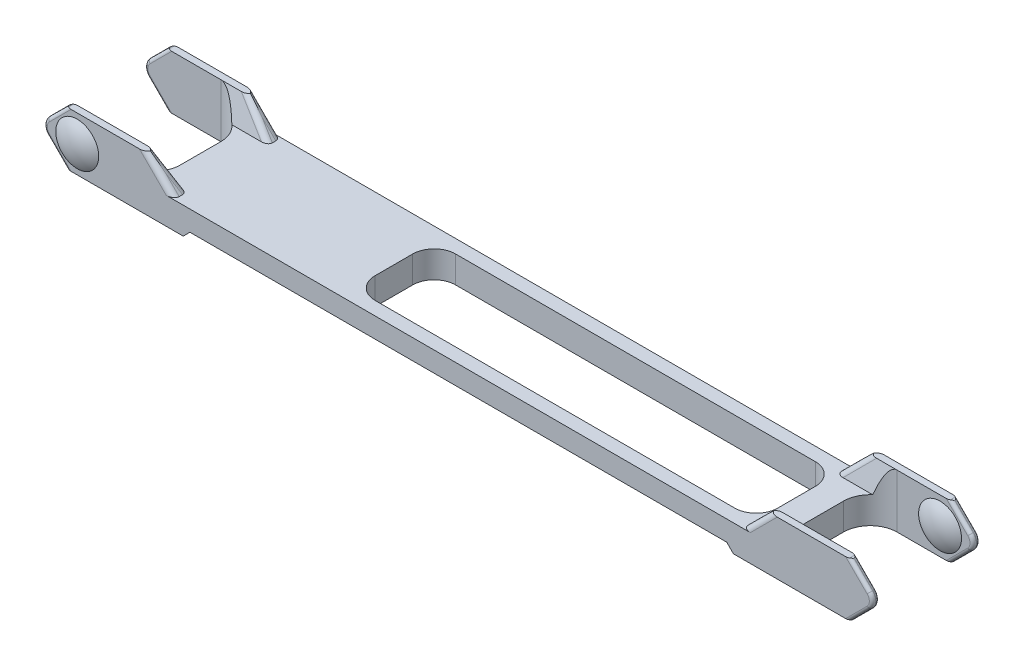
SolidWorks part; units mm, degrees
ref_plane "Front Plane" through (0, 0, 0) normal (0, 0, 1) x (1, 0, 0)
ref_plane "Top Plane" through (0, 0, 0) normal (0, 1, 0) x (1, 0, 0)
ref_plane "Right Plane" through (0, 0, 0) normal (1, 0, 0) x (0, 0, -1)
sketch "Sketch1" plane through (0, 0, 0) normal (0, 1, 0) x (1, 0, 0)
  line L0 (-73.66, 12.7) -> (-73.66, -12.7) construction
  line L1 (-99.06, -12.7) -> (99.06, -12.7)
  line L2 (-99.06, -12.7) -> (-99.06, -11.1125)
  line L3 (-99.06, 12.7) -> (99.06, 12.7)
  line L5 (-99.06, -12.7) -> (99.06, 12.7) construction
  line L6 (-99.06, 12.7) -> (99.06, -12.7) construction
  line L7 (-99.06, 11.1125) -> (-80.01, 11.1125)
  line L8 (-73.66, 4.7625) -> (-73.66, -4.7625)
  line L9 (-80.01, -11.1125) -> (-99.06, -11.1125)
  line L10 (-99.06, 11.1125) -> (-99.06, 12.7)
  line L11 (0, 0) -> (0, 12.7) construction
  line L12 (99.06, 12.7) -> (99.06, 11.1125)
  line L13 (99.06, -12.7) -> (99.06, -11.1125)
  line L14 (80.01, -11.1125) -> (99.06, -11.1125)
  line L15 (73.66, 4.7625) -> (73.66, -4.7625)
  line L16 (99.06, 11.1125) -> (80.01, 11.1125)
  arc A0 (-73.66, -4.7625) -> (-80.01, -11.1125) centre (-80.01, -4.7625) cw
  arc A1 (-80.01, 11.1125) -> (-73.66, 4.7625) centre (-80.01, 4.7625) cw
  arc A2 (73.66, -4.7625) -> (80.01, -11.1125) centre (80.01, -4.7625) ccw
  arc A3 (80.01, 11.1125) -> (73.66, 4.7625) centre (80.01, 4.7625) ccw
  point P0 (0, 0)
  point P14 (-73.66, -11.1125)
  point P17 (-73.66, 11.1125)
  dimension "D6" = 6.35
  dimension "D1" = 198.12
  dimension "D2" = 25.4
  dimension "D3" = 25.4
  dimension "D4" = 1.5875
  dimension "D5" = 1.5875
extrude "Boss-Extrude1" add sketch "Sketch1" along normal blind 12.7
sketch "Sketch3" plane through (-99.06, 0, 0) normal (-1, 0, 0) x (0, 0, 1)
  line L7 (11.1125, 12.7) -> (4.7625, 12.7) construction
  line L8 (-4.7625, 12.7) -> (4.7625, 12.7) construction
  line L9 (-4.7625, 12.7) -> (-11.1125, 12.7) construction
  line L19 (11.1125, 12.7) -> (4.7625, 12.7)
  line L20 (-4.7625, 12.7) -> (4.7625, 12.7)
  line L21 (-4.7625, 12.7) -> (-11.1125, 12.7)
  line L24 (0, 0) -> (0, 12.7) construction
  line L25 (-12.7, 6.35) -> (12.7, 6.35) construction
  line L26 (-9.525, 6.35) -> (9.525, 6.35)
  line L27 (-11.1125, 12.7) -> (-9.525, 6.35)
  line L28 (9.525, 6.35) -> (11.1125, 12.7)
  point P17 (0, 6.35)
  dimension "D1" = 19.05
  dimension "D2" = 6.35
extrude "Cut-Extrude2" cut sketch "Sketch3" against normal through all
sketch "Sketch2" plane through (0, 0, 12.7) normal (0, 0, 1) x (1, 0, 0)
  line L0 (-97.2639, 8.1461) -> (-92.71, 12.7)
  line L1 (-97.2639, 4.5539) -> (-92.71, 0)
  line L2 (-73.66, 12.7) -> (-73.66, 0) construction
  line L3 (0, 0) -> (0, 12.7) construction
  line L4 (-99.06, 0) -> (99.06, 0)
  line L5 (99.06, 0) -> (99.06, 12.7)
  line L6 (99.06, 12.7) -> (-99.06, 12.7)
  line L7 (-99.06, 12.7) -> (-99.06, 0)
  line L8 (-99.06, 0) -> (-92.71, 0)
  line L9 (99.06, 0) -> (99.06, 12.7)
  line L10 (99.06, 12.7) -> (92.71, 12.7)
  line L11 (-99.06, 12.7) -> (-99.06, 0)
  line L12 (73.66, 12.7) -> (73.66, 0) construction
  line L13 (97.2639, 4.5539) -> (92.71, 0)
  line L14 (97.2639, 8.1461) -> (92.71, 12.7)
  line L15 (99.06, 12.7) -> (99.06, 0)
  line L16 (-99.06, 0) -> (-99.06, 12.7)
  line L17 (-99.06, 6.35) -> (99.06, 6.35) construction
  line L18 (-73.66, 12.7) -> (-67.31, 6.35)
  line L19 (-67.31, 6.35) -> (67.31, 6.35)
  line L20 (67.31, 6.35) -> (73.66, 12.7)
  line L21 (-92.71, 12.7) -> (-99.06, 12.7)
  line L22 (92.71, 0) -> (99.06, 0)
  line L23 (73.66, 12.7) -> (-73.66, 12.7)
  arc A0 (97.2639, 4.5539) -> (97.2639, 8.1461) centre (95.4679, 6.35) ccw
  arc A1 (-97.2639, 8.1461) -> (-97.2639, 4.5539) centre (-95.4679, 6.35) ccw
  line M12 (-99.06, 0) -> (99.06, 0)
  line M13 (99.06, 0) -> (99.06, 12.7)
  line M14 (99.06, 12.7) -> (-99.06, 12.7)
  line M15 (-99.06, 12.7) -> (-99.06, 0)
  dimension "D7" = 2.54
  dimension "D2" = 45
  dimension "D3" = 45
  dimension "D4" = 25.4
  dimension "D5" = 45
  dimension "D6" = 45
  dimension "D1" = 0
extrude "Cut-Extrude1" cut sketch "Sketch2" against normal through all contours L19 L20 L18 M14 | A0 L13 L14 M12 M13 M14 | A1 L0 L1 M14 M15 M12 region at (-98.1499, 6.35, 12.7) region at (0, 9.5727, 12.7) region at (95.0874, 2.1766, 12.7)
ref_plane "Plane1" through (-90.17, 0, 0) normal (-1, 0, 0) x (0, 0, 1)
sketch "Sketch4" plane through (-90.17, 0, 0) normal (-1, 0, 0) x (0, 0, 1)
  line L0 (0, 6.35) -> (17.6113, 6.35) construction
  line L1 (4.7625, 6.35) -> (-4.7625, 6.35) construction
  line L2 (12.7, 6.35) -> (12.7, 11.43)
  line L3 (12.7, 8.1461) -> (12.7, 12.7) construction
  line L4 (12.7, 6.35) -> (14.2875, 6.35)
  arc A0 (12.7, 11.43) -> (14.2875, 6.35) centre (5.3658, 6.35) cw
  dimension "D3" = 8.9217
  dimension "D1" = 5.08
  dimension "D2" = 1.5875
revolve "Revolve1" add sketch "Sketch4" angle 360 about L0
ref_plane "Plane2" through (0, 0, 0) normal (0, 0, 1) x (1, 0, 0)
mirror "Mirror1" about plane through (0, 0, 0) normal (0, 0, 1) of "Revolve1"
ref_plane "Plane3" through (90.17, 0, 0) normal (1, 0, 0) x (0, 0, -1)
sketch "Sketch5" plane through (90.17, 0, 0) normal (1, 0, 0) x (0, 0, -1)
  line L0 (0, 6.35) -> (15.4068, 6.35) construction
  line L1 (4.7625, 6.35) -> (-4.7625, 6.35) construction
  line L2 (11.1125, 6.35) -> (11.1125, 11.43)
  line L3 (11.1125, 12.7) -> (11.1125, 0) construction
  line L4 (11.1125, 12.7) -> (11.1125, 8.1461) construction
  line L5 (11.1125, 6.35) -> (9.525, 6.35)
  arc A0 (11.1125, 11.43) -> (9.525, 6.35) centre (18.4467, 6.35) ccw
  dimension "D3" = 8.9217
  dimension "D1" = 5.08
  dimension "D2" = 1.5875
revolve "Revolve2" add sketch "Sketch5" angle 360 about L0
mirror "Mirror2" about plane through (0, 0, 0) normal (0, 0, 1) of "Revolve2"
ref_plane "Plane4" through (0, 0, 0) normal (1, 0, 0) x (0, 0, -1)
sketch "Sketch6" plane through (0, 0, 0) normal (1, 0, 0) x (0, 0, -1)
  line L5 (-12.7, 0) -> (-11.1125, 0)
  line L6 (-11.1125, 0) -> (-12.7, 0) construction
  line L7 (-11.1125, 0) -> (-12.7, 1.5875)
  line L8 (-12.7, 11.43) -> (-12.7, 1.27) construction
  line L9 (-12.7, 1.5875) -> (-12.7, 0)
  line L10 (0, 0) -> (0, 6.35) construction
  line L11 (-4.7625, 6.35) -> (4.7625, 6.35) construction
  line L12 (11.1125, 0) -> (12.7, 1.5875)
  line L13 (12.7, 0) -> (11.1125, 0)
  line L14 (12.7, 1.5875) -> (12.7, 0)
  dimension "D1" = 1.5875
  dimension "D2" = 1.5875
extrude "Cut-Extrude3" cut sketch "Sketch6" against normal mid plane 127
chamfer "Chamfer1" distance 1.5875 angle 45 4 edges at (63.5, 0, 11.9062) (63.5, 0, -11.9062) (-63.5, 0, -11.9062) (-63.5, 0, 11.9062)
fillet "Fillet1" radius 0.762 28 edges at (94.987, 2.277, -12.7) (98.0079, 6.35, -12.7) (94.987, 2.277, -11.1125) (98.0079, 6.35, -11.1125) (94.987, 2.277, 12.7) (98.0079, 6.35, 12.7) (94.987, 2.277, 11.1125) (98.0079, 6.35, 11.1125) (-94.987, 2.277, -11.1125) (-98.0079, 6.35, -11.1125) (-94.987, 2.277, -12.7) (-98.0079, 6.35, -12.7) (-94.987, 2.277, 11.1125) (-98.0079, 6.35, 11.1125) (-94.987, 2.277, 12.7) (-98.0079, 6.35, 12.7) (92.71, 12.7, -11.9062) (94.987, 10.423, -12.7) (94.987, 10.423, -11.1125) (94.987, 10.423, 12.7) (92.71, 12.7, 11.9063) (94.987, 10.423, 11.1125) (-94.987, 10.423, -11.1125) (-94.987, 10.423, -12.7) (-92.71, 12.7, -11.9062) (-94.987, 10.423, 11.1125) (-92.71, 12.7, 11.9063) (-94.987, 10.423, 12.7)
fillet "Fillet2" radius 1.27 8 edges at (-70.485, 9.525, -12.7) (-70.485, 9.525, -10.3188) (-70.485, 9.525, 10.3187) (-70.485, 9.525, 12.7) (70.485, 9.525, -12.7) (70.485, 9.525, -10.3188) (70.485, 9.525, 12.7) (70.485, 9.525, 10.3187)
sketch "Sketch7" plane through (0, 6.35, 0) normal (0, 1, 0) x (1, 0, 0)
  line L0 (-69.1061, 12.7) -> (69.1061, 12.7) construction
  line L1 (-22.86, 9.525) -> (62.23, 9.525)
  line L2 (-27.94, 4.445) -> (-27.94, -4.445)
  line L3 (-22.86, -9.525) -> (62.23, -9.525)
  line L4 (67.31, 4.445) -> (67.31, -4.445)
  line L5 (-69.1061, -12.7) -> (69.1061, -12.7) construction
  line L6 (73.66, 4.7625) -> (73.66, -4.7625) construction
  arc A0 (-27.94, -4.445) -> (-22.86, -9.525) centre (-22.86, -4.445) ccw
  arc A1 (-22.86, 9.525) -> (-27.94, 4.445) centre (-22.86, 4.445) ccw
  arc A2 (62.23, -9.525) -> (67.31, -4.445) centre (62.23, -4.445) ccw
  arc A3 (62.23, 9.525) -> (67.31, 4.445) centre (62.23, 4.445) cw
  dimension "D5" = 5.08
  dimension "D1" = 3.175
  dimension "D2" = 3.175
  dimension "D3" = 6.35
  dimension "D4" = 101.6
extrude "Cut-Extrude4" cut sketch "Sketch7" against normal through all
